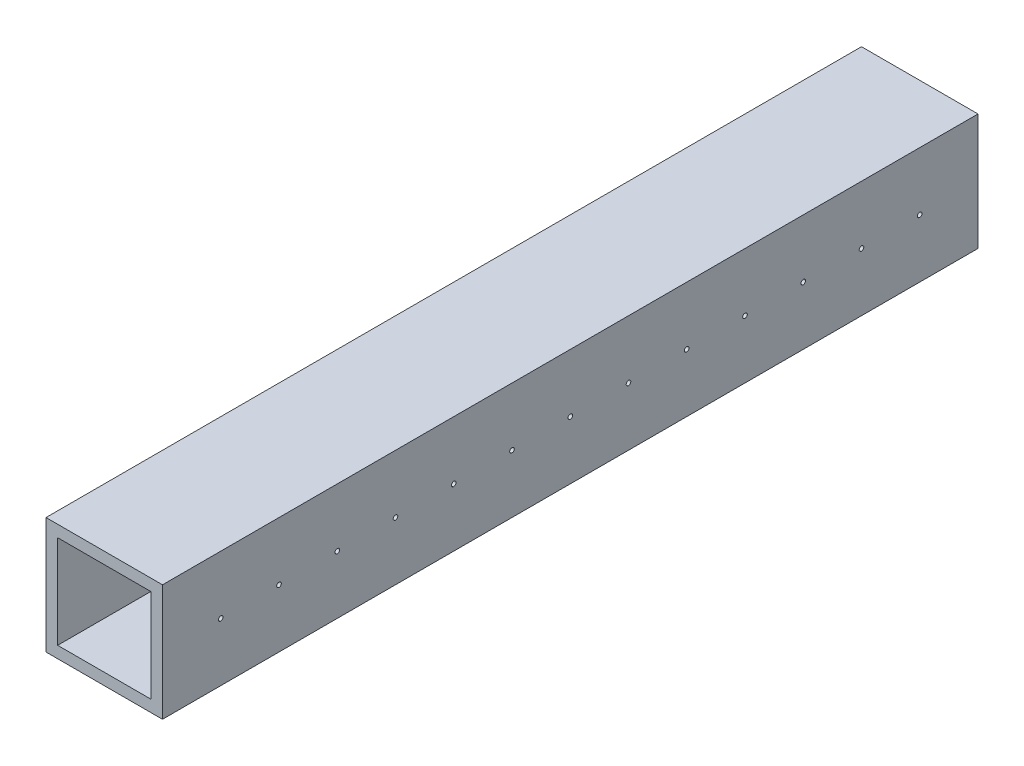
SolidWorks part; units mm, degrees
ref_plane "Front Plane" through (0, 0, 0) normal (0, 0, 1) x (1, 0, 0)
ref_plane "Top Plane" through (0, 0, 0) normal (0, 1, 0) x (1, 0, 0)
ref_plane "Right Plane" through (0, 0, 0) normal (1, 0, 0) x (0, 0, -1)
sketch "Sketch1" plane through (0, 0, 0) normal (0, 0, 1) x (1, 0, 0)
  line L1 (2.0562, 11.0067) -> (22.3762, 11.0067)
  line L2 (2.0562, 11.0067) -> (2.0562, -9.3133)
  line L3 (2.0562, -9.3133) -> (22.3762, -9.3133)
  line L4 (22.3762, 11.0067) -> (22.3762, -9.3133)
  line L5 (-0.4838, 13.5467) -> (24.9162, 13.5467)
  line L6 (-0.4838, 13.5467) -> (-0.4838, -11.8533)
  line L7 (-0.4838, -11.8533) -> (24.9162, -11.8533)
  line L8 (24.9162, 13.5467) -> (24.9162, -11.8533)
  dimension "D1" = 25.4
  dimension "D2" = 25.4
  dimension "D3" = 2.54
  dimension "D4" = 2.54
  dimension "D5" = 2.54
  dimension "D6" = 2.54
extrude "Boss-Extrude1" add sketch "Sketch1" along normal blind 177.8
sketch "Sketch2" plane through (24.9162, 0, 0) normal (1, 0, 0) x (0, 0, -1)
  line L0 (-177.8, 13.5467) -> (0, 13.5467) construction
  line L1 (-177.8, -11.8533) -> (-177.8, 13.5467) construction
  circle A0 centre (-165.1, 0.8467) radius 0.5
  circle A1 centre (-152.4, 0.8467) radius 0.5
  circle A2 centre (-139.7, 0.8467) radius 0.5
  circle A3 centre (-127, 0.8467) radius 0.5
  circle A4 centre (-114.3, 0.8467) radius 0.5
  circle A5 centre (-101.6, 0.8467) radius 0.5
  circle A6 centre (-88.9, 0.8467) radius 0.5
  circle A7 centre (-76.2, 0.8467) radius 0.5
  circle A8 centre (-63.5, 0.8467) radius 0.5
  circle A9 centre (-50.8, 0.8467) radius 0.5
  circle A10 centre (-38.1, 0.8467) radius 0.5
  circle A11 centre (-25.4, 0.8467) radius 0.5
  circle A12 centre (-12.7, 0.8467) radius 0.5
  dimension "D1" = 1
  dimension "D2" = 12.7
  dimension "D3" = 12.7
  dimension "D4" = 13
extrude "Cut-Extrude1" cut sketch "Sketch2" against normal through all both and the other way through all
